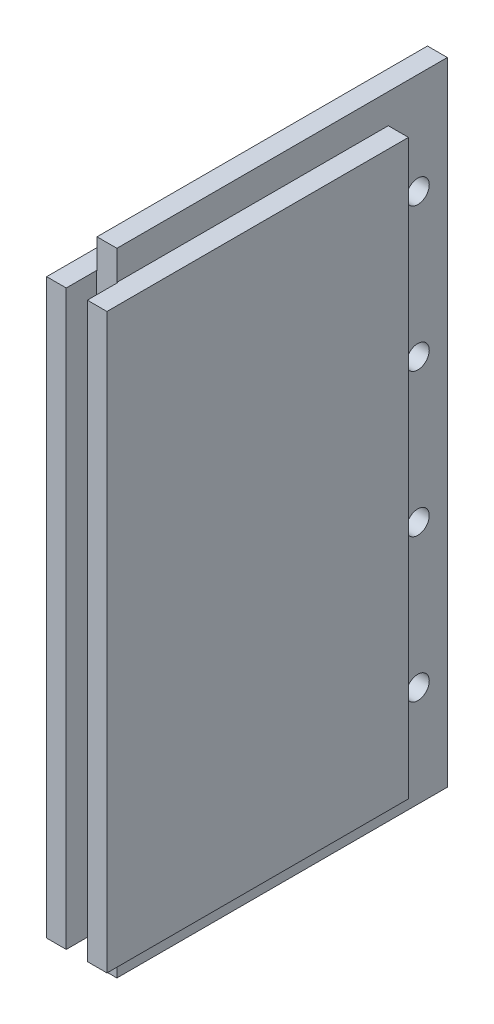
SolidWorks part; units mm, degrees
ref_plane "Front Plane" through (0, 0, 0) normal (1, 0, 0) x (0, 1, 0)
ref_plane "Top Plane" through (0, 0, 0) normal (0, 0, 1) x (0, 1, 0)
ref_plane "Right Plane" through (0, 0, 0) normal (0, 1, 0) x (-1, 0, 0)
sketch "Sketch2" plane through (0, 0, 0) normal (1, 0, 0) x (0, 1, 0)
  line L1 (0, 0) -> (95, 0)
  line L2 (0, 0) -> (0, 50)
  line L3 (0, 50) -> (95, 50)
  line L4 (95, 0) -> (95, 50)
  dimension "D1" = 95
  dimension "D2" = 50
extrude "Boss-Extrude1" add sketch "Sketch2" against normal blind 10
sketch "Sketch3" plane through (0, 95, 0) normal (0, 1, 0) x (-1, 0, 0)
  line L1 (0, 0) -> (3.35, 0) construction
  line L2 (0, 0) -> (0, -9.8) construction
  line L3 (0, -9.8) -> (3.35, -9.8) construction
  line L4 (3.35, 0) -> (3.35, -9.8) construction
  line L5 (10, 0) -> (6.65, 0) construction
  line L6 (10, 0) -> (10, -9.8) construction
  line L7 (10, -9.8) -> (6.65, -9.8) construction
  line L8 (6.65, 0) -> (6.65, -9.8) construction
  line L9 (6.65, -9.8) -> (3.35, -9.8)
  line L10 (6.65, -9.8) -> (6.65, 0)
  line L11 (6.65, 0) -> (3.35, 0)
  line L12 (3.35, -9.8) -> (3.35, 0)
  dimension "D1" = 3.35
  dimension "D2" = 3.35
  dimension "D3" = 9.8
extrude "Boss-Extrude2" add sketch "Sketch3" against normal up to surface (95 mm away) up to face at (-5, 0, 25)
sketch "Sketch4" plane through (0, 95, 0) normal (0, 1, 0) x (-1, 0, 0)
  line L1 (0, 50) -> (3.35, 50) construction
  line L2 (0, 50) -> (0, -9.8) construction
  line L3 (0, -9.8) -> (3.35, -9.8) construction
  line L4 (3.35, 50) -> (3.35, -9.8) construction
  line L5 (6.65, -9.8) -> (10, -9.8) construction
  line L6 (6.65, -9.8) -> (6.65, 50) construction
  line L7 (6.65, 50) -> (10, 50) construction
  line L8 (10, -9.8) -> (10, 50) construction
  line L9 (3.35, 50) -> (6.65, 50)
  line L10 (3.35, 50) -> (3.35, -9.8)
  line L11 (3.35, -9.8) -> (6.65, -9.8)
  line L12 (6.65, 50) -> (6.65, -9.8)
extrude "Boss-Extrude3" add sketch "Sketch4" along normal blind 4.9
ref_plane "Plane1" through (0, 47.5, 0) normal (0, 1, 0) x (1, 0, 0)
mirror "Mirror1" about plane through (0, 47.5, 0) normal (0, 1, 0) of "Boss-Extrude3"
sketch "Sketch5" plane through (-3.35, 0, 0) normal (1, 0, 0) x (0, 1, 0)
  line L0 (-4.9, -9.8) -> (99.9, -9.8) construction
  line L1 (0, 0) -> (11.875, 0) construction
  line L2 (0, 0) -> (0, -9.8) construction
  line L3 (0, -9.8) -> (11.875, -9.8) construction
  line L4 (11.875, 0) -> (11.875, -9.8) construction
  circle A0 centre (11.875, -4.9) radius 1.9
  dimension "D2" = 3.8
  dimension "D1" = 11.875
extrude "Cut-Extrude1" cut sketch "Sketch5" against normal up to next
pattern_linear "LPattern1" count 4 spacing 23.75 along (0, 1, 0) of "Cut-Extrude1"
sketch "Sketch7" plane through (0, 0, 50) normal (0, 0, 1) x (1, 0, 0)
  line L1 (-6.75, 99.9) -> (-3.25, 99.9)
  line L2 (-6.75, 99.9) -> (-6.75, -4.9)
  line L3 (-6.75, -4.9) -> (-3.25, -4.9)
  line L4 (-3.25, 99.9) -> (-3.25, -4.9)
  line L6 (-10, 95) -> (-10, 0) construction
  line L7 (-6.75, 99.9) -> (-10, 99.9) construction
  line L8 (-6.75, 99.9) -> (-6.75, -4.9) construction
  line L9 (-6.75, -4.9) -> (-10, -4.9) construction
  line L10 (-10, 99.9) -> (-10, -4.9) construction
  line L11 (-3.25, -4.9) -> (0, -4.9) construction
  line L12 (-3.25, -4.9) -> (-3.25, 99.9) construction
  line L13 (-3.25, 99.9) -> (0, 99.9) construction
  line L14 (0, -4.9) -> (0, 99.9) construction
  line L15 (0, 95) -> (0, 0) construction
  line L16 (-6.65, 99.9) -> (-3.35, 99.9) construction
  line L17 (-6.65, -4.9) -> (-3.35, -4.9) construction
  dimension "D1" = 3.25
  dimension "D2" = 3.25
extrude "Cut-Extrude6" cut sketch "Sketch7" against normal blind 5
sketch "Sketch8" plane through (-10, 0, 0) normal (-1, 0, 0) x (0, -1, 0)
  line L1 (-95, 45) -> (0, 45)
  line L2 (-95, 45) -> (-95, 0)
  line L3 (-95, 0) -> (0, 0)
  line L4 (0, 45) -> (0, 0)
  line L5 (-90, 40) -> (-90, 5)
  line L6 (-90, 5) -> (-5, 5)
  line L7 (-5, 40) -> (-5, 5)
  line L8 (-90, 40) -> (-5, 40)
  dimension "D1" = 5
extrude "Cut-Extrude7" cut sketch "Sketch8" against normal blind 5 contours L8 L5 L6 L7 region at (-10, 47.5, 22.5)
chamfer "Chamfer1" distance 5 distance2 2.5 4 edges at (-10, 5, 22.5) (-10, 47.5, 5) (-10, 90, 22.5) (-10, 47.5, 40) first distance on face at (-7.5, 5, 22.5) first distance on face at (-7.5, 47.5, 5) first distance on face at (-7.5, 90, 22.5) first distance on face at (-7.5, 47.5, 40)
equation "\"whitekey_cutout_length\"= 101.5"
equation "\"whitekey_spacing\"=1.25"
equation "\"key_mount_recess_length\"=50"
equation "\"key_mount_recess_height\"=12.5"
equation "\"key_mount_recess_depth\"=1.5"
equation "\"wall_thickness\"=10"
equation "\"guide_brace_height\"=20"
equation "\"guide_brace_thickness\"=2"
equation "\"dowel_recess_depth\"=10"
equation "\"dowel_recess_offset\"=3.25"
equation "\"dowel_insert_tolerance\"=0.1"
equation "\"base_mount_height\"=40"
equation "\"base_rear_length\"=80"
equation "\"base_front_length\"=111.5"
equation "\"screw_hole_wall_offset\"=7.25"
equation "\"screw_hole_edge_inset\"=\"dowel_recess_depth\"/2"
equation "\"screw_hole_diameter\"=3.8"
equation "\"screw_head_hole_diameter\"=6.7"
equation "\"screw_nut_hole_side_len\"=3.5"
equation "\"screw_nut_recess_offset\"=0.35"
equation "\"screw_head_and_nut_recess_depth\"=2.5"
equation "\"screw_shaft_diameter\"=3.5"
equation "\"switch_board_width\"=30"
equation "\"switch_board_thickness\"=1.6"
equation "\"switch_board_wall_offset\"=11.5"
equation "\"heatset_insert_hole_diameter\"=4.8"
equation "\"heatset_insert_hole_depth\"=3.8"
equation "\"front_rear_panel_width\"=23.75"
equation "\"front_panel_height\"=24"
equation "\"front_rear_panel_recess_depth\"=5"
equation "\"rod_diameter\"=5"
equation "\"rod_head_diameter\"=8"
equation "\"rod_length_adj\"=0.5"
equation "\"rod_insert_length\"=2.8"
equation "\"switch_black_key_mount_height\"=8"
equation "\"switch_white_key_mount_height\"=3"
equation "\"side_panel_depth\"=35"
equation "\"interface_panel_height\"=135"
equation "\"interface_panel_roof_length\"=50"
equation "\"D1@Sketch2\"=\"front_rear_panel_width\"*4"
equation "\"D2@Sketch2\"=\"base_mount_height\"+\"wall_thickness\""
equation "\"D1@Boss-Extrude1\"=\"wall_thickness\""
equation "\"D1@Sketch3\"=\"dowel_recess_offset\"+\"dowel_insert_tolerance\""
equation "\"D2@Sketch3\"=\"dowel_recess_offset\"+\"dowel_insert_tolerance\""
equation "\"D3@Sketch3\"=\"dowel_recess_depth\"-\"dowel_insert_tolerance\"*2"
equation "\"D1@Boss-Extrude3\"=\"front_rear_panel_recess_depth\"-\"dowel_insert_tolerance\""
equation "\"D1@Sketch5\"=\"front_rear_panel_width\"/2"
equation "\"D2@Sketch5\"=\"screw_hole_diameter\""
equation "\"D3@LPattern1\"=\"front_rear_panel_width\""
equation "\"D1@Cut-Extrude6\"=\"front_rear_panel_recess_depth\""
equation "\"D1@Sketch7\"=\"dowel_recess_offset\""
equation "\"D2@Sketch7\"=\"dowel_recess_offset\""
equation "\"D1@Cut-Extrude7\"=\"wall_thickness\"/2"
